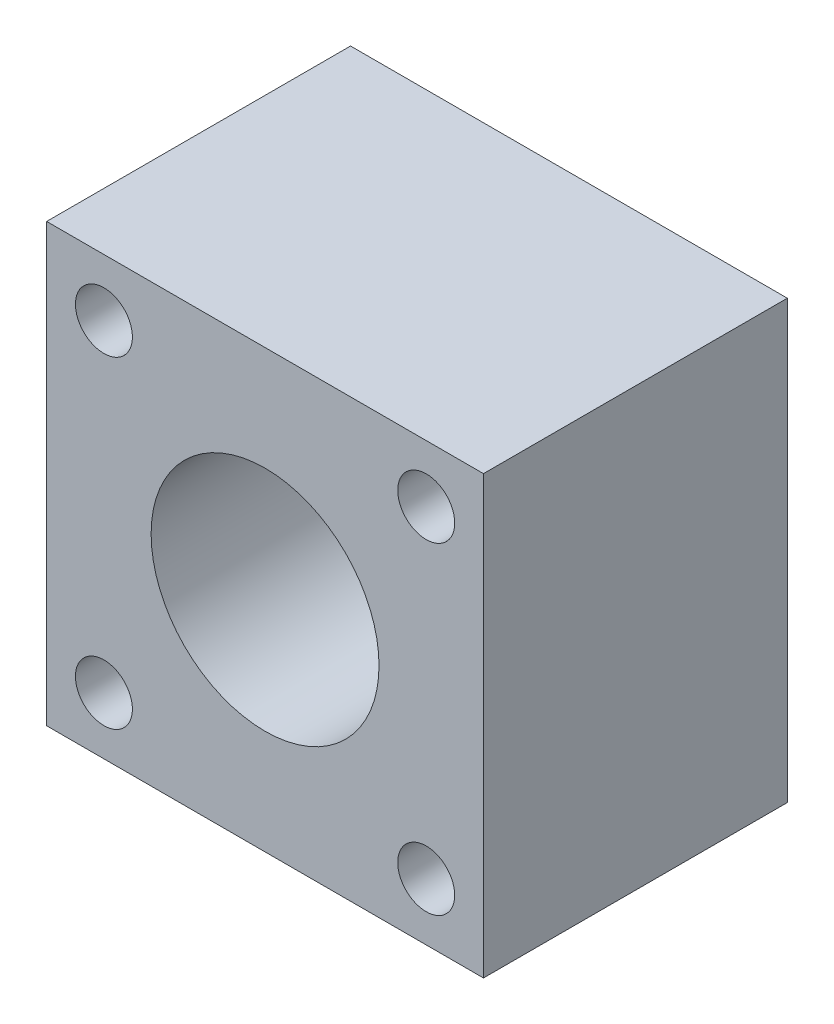
SolidWorks part; units mm, degrees
note: The reader was unsure of these and kept them because the rebuilt part matched: shared geometry of "Sketch2<14>".
ref_plane "Front Plane" through (0, 0, 0) normal (0, 0, 1) x (1, 0, 0)
ref_plane "Top Plane" through (0, 0, 0) normal (0, 1, 0) x (1, 0, 0)
ref_plane "Right Plane" through (0, 0, 0) normal (1, 0, 0) x (0, 0, -1)
sketch "Sketch2" plane through (0, 0, 0) normal (0, 0, 1) x (1, 0, 0)
  line L1 (-11.5, 11.5) -> (11.5, 11.5)
  line L2 (-11.5, 11.5) -> (-11.5, -11.5)
  line L3 (-11.5, -11.5) -> (11.5, -11.5)
  line L4 (11.5, 11.5) -> (11.5, -11.5)
  circle A0 centre (0, 0) radius 7.5
  circle A1 centre (0, 0) radius 6
  circle A3 centre (8.4853, 8.4853) radius 1.5
  circle A4 centre (8.4853, -8.4853) radius 1.5
  circle A5 centre (-8.4853, -8.4853) radius 1.5
  circle A6 centre (-8.4853, 8.4853) radius 1.5
extrude "Extrude8" add sketch "Sketch2" along normal blind 11
extrude "Extrude9" add sketch "Sketch2<14>" along normal blind 11 and the other way blind 5
sketch "Sketch2<14>" plane through (0, 0, 0) normal (0, 0, 1) x (1, 0, 0) same geometry as "Sketch2"
